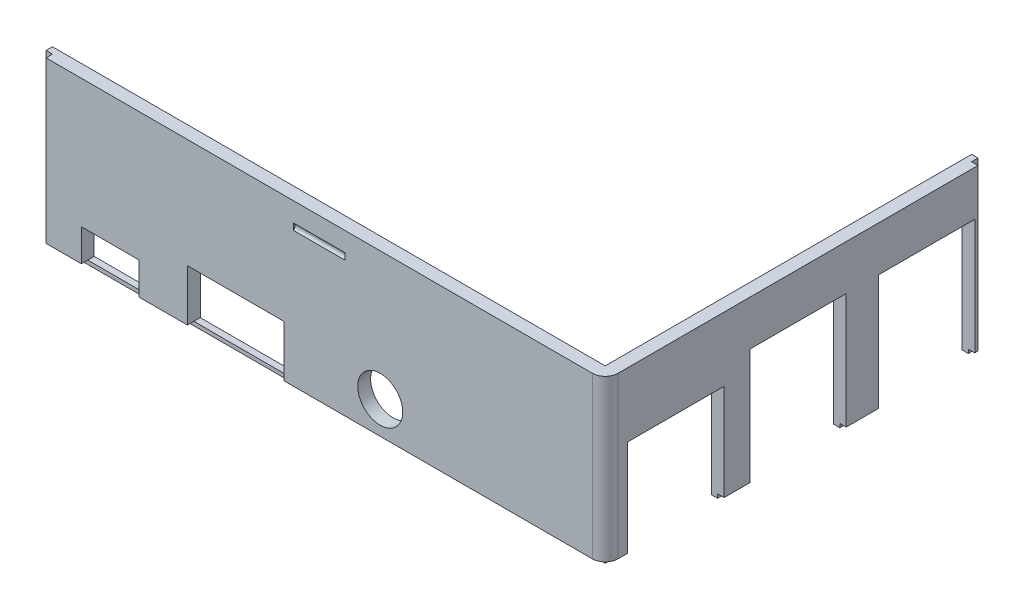
SolidWorks part; units mm, degrees
ref_plane "Přední rovina" through (0, 0, 0) normal (0, 0, 1) x (1, 0, 0)
ref_plane "Horní rovina" through (0, 0, 0) normal (0, 1, 0) x (1, 0, 0)
ref_plane "Pravá rovina" through (0, 0, 0) normal (1, 0, 0) x (0, 0, -1)
sketch "Skica1" plane through (0, 0, 0) normal (0, 1, 0) x (1, 0, 0)
  line L1 (0, 0) -> (88, 0)
  line L2 (0, 0) -> (0, 2)
  line L3 (0, 2) -> (88, 2)
  line L4 (88, 0) -> (88, 2)
  line L9 (88, 2) -> (86, 2)
  line L10 (88, 2) -> (88, 59)
  line L11 (88, 59) -> (86, 59)
  line L12 (86, 2) -> (86, 59)
  line L17 (0, 0) -> (1, 0)
  line L18 (0, 0) -> (0, 1)
  line L19 (0, 1) -> (1, 1)
  line L20 (1, 0) -> (1, 1)
  line L21 (88, 59) -> (87, 59)
  line L22 (88, 59) -> (88, 58)
  line L23 (88, 58) -> (87, 58)
  line L24 (87, 59) -> (87, 58)
  dimension "D1" = 2
  dimension "D2" = 88
  dimension "D3" = 1
  dimension "D4" = 57
  dimension "D5" = 2
  dimension "D6" = 1
extrude "Přidat vysunutím1" add sketch "Skica1" along normal blind 25 contours L24 L11 L12 L3 L10 L23 | L20 L1 L4 L3 L2 L19 region at (44.2486, 0, -1.0029) region at (86.9956, 0, -30.2522)
sketch "Skica2" plane through (0, 0, 0) normal (0, -1, 0) x (1, 0, 0)
  line L0 (0, -1) -> (0, -2) construction
  line L1 (0, -1) -> (86, -1)
  line L2 (0, -1) -> (0, -2)
  line L3 (0, -2) -> (86, -2)
  line L4 (86, -1) -> (86, -2)
  line L5 (87, -59) -> (86, -59)
  line L6 (87, -59) -> (87, -1)
  line L7 (87, -1) -> (86, -1)
  line L8 (86, -59) -> (86, -1)
  line L9 (0, -1) -> (1, -1) construction
extrude "Přidat vysunutím2" add sketch "Skica2" along normal blind 0.6 contours L4 L3 L2 L1 | L8 L5 L6 L7
sketch "Skica5" plane through (0, 0, 0) normal (0, 0, 1) x (1, 0, 0)
  line L0 (1, 0) -> (88, 0) construction
  line L1 (6.5, 5) -> (15.5, 5)
  line L2 (6.5, 5) -> (6.5, 0)
  line L3 (6.5, 0) -> (15.5, 0)
  line L4 (15.5, 5) -> (15.5, 0)
  line L5 (11, 5) -> (11, 0) construction
  line L6 (0, 25) -> (0, 0) construction
  line L7 (0, -0.6) -> (0, 25) construction
  line L8 (23, 0) -> (38, 0)
  line L9 (23, 0) -> (23, 8)
  line L10 (23, 8) -> (38, 8)
  line L11 (38, 0) -> (38, 8)
  line L12 (1, 0) -> (87, 0) construction
  circle A0 centre (53, 5) radius 3.5
  dimension "D7" = 7
  dimension "D9" = 5
  dimension "D1" = 5
  dimension "D2" = 9
  dimension "D3" = 11
  dimension "D4" = 23
  dimension "D5" = 15
  dimension "D6" = 8
  dimension "D8" = 53
extrude "Odebrat vysunutím1" cut sketch "Skica5" against normal up to next
sketch "Skica6" plane through (88, 0, 0) normal (1, 0, 0) x (0, 0, -1)
  line L1 (3.5, -0.6) -> (18.5, -0.6)
  line L2 (3.5, -0.6) -> (3.5, 15)
  line L3 (3.5, 15) -> (18.5, 15)
  line L4 (18.5, -0.6) -> (18.5, 15)
  line L9 (42.5, -0.6) -> (57.5, -0.6)
  line L10 (42.5, -0.6) -> (42.5, 18)
  line L11 (42.5, 18) -> (57.5, 18)
  line L12 (57.5, -0.6) -> (57.5, 18)
  line L13 (11, 15) -> (11, -0.6) construction
  line L18 (22.5, -0.6) -> (37.5, -0.6)
  line L19 (22.5, -0.6) -> (22.5, 18)
  line L20 (22.5, 18) -> (37.5, 18)
  line L21 (37.5, -0.6) -> (37.5, 18)
  line L22 (30, 18) -> (30, -0.6) construction
  line L24 (50, 18) -> (50, -0.6) construction
  line L27 (1, -0.6) -> (1, 0) construction
  line L28 (59, -0.6) -> (1, -0.6) construction
  line L29 (0, 0) -> (58, 0) construction
  line L30 (58, 0) -> (1, 0) construction
  line L31 (59, -0.6) -> (59, 25) construction
  point P28 (59, 12.2)
  dimension "D1" = 10
  dimension "D2" = 29
  dimension "D3" = 9
  dimension "D4" = 15
  dimension "D5" = 15
  dimension "D6" = 15
  dimension "D7" = 18
  dimension "D8" = 15
  dimension "D9" = 18
extrude "Odebrat vysunutím2" cut sketch "Skica6" against normal up to next
fillet "Fillet1" radius 2 1 edges at (88, 12.5, 0)
sketch "Sketch1" plane through (88, 0, 0) normal (1, 0, 0) x (0, 0, -1)
  line L0 (0, 21.5) -> (-0.4, 21.5)
  line L1 (0, 0) -> (0, 25) construction
  line L2 (2, 25) -> (58, 25) construction
  line L3 (0, 22) -> (0, 21)
  arc A0 (0, 22) -> (0, 21) centre (-0.4, 21.5) cw
  dimension "D2" = 1
  dimension "D1" = 0.4
  dimension "D3" = 4
extrude "Cut-Extrude1" cut sketch "Sketch1" against normal blind 8 from offset 40.5 contours A0 L3 region at (88, 21.5, -0.0979) offset against normal yes
